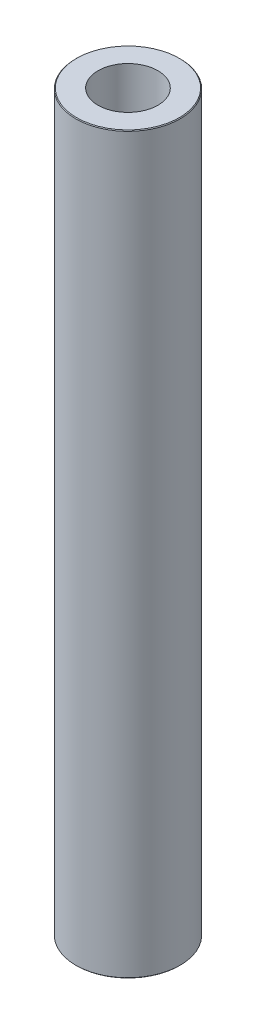
SolidWorks part; units mm, degrees
ref_plane "Front Plane" through (0, 0, 0) normal (0, 0, 1) x (1, 0, 0)
ref_plane "Top Plane" through (0, 0, 0) normal (0, 1, 0) x (1, 0, 0)
ref_plane "Right Plane" through (0, 0, 0) normal (1, 0, 0) x (0, 0, -1)
sketch "Sketch1" plane through (0, 0, 0) normal (0, 1, 0) x (1, 0, 0)
  circle A0 centre (0, 0) radius 35
  dimension "SHAFT_OD" = 70
extrude "Boss-Extrude1" add sketch "Sketch1" along normal blind 493.1632
sketch "Sketch2" plane through (0, 0, 0) normal (0, 1, 0) x (1, 0, 0)
  circle A0 centre (0, 0) radius 20.1193
  dimension "BORE_D" = 40.2386
extrude "Cut-Extrude1" cut sketch "Sketch2" along normal through all
chamfer "Chamfer1" distance 0.4859 angle 45 2 edges at (0, 493.1632, 35) (0, 0, 35)
